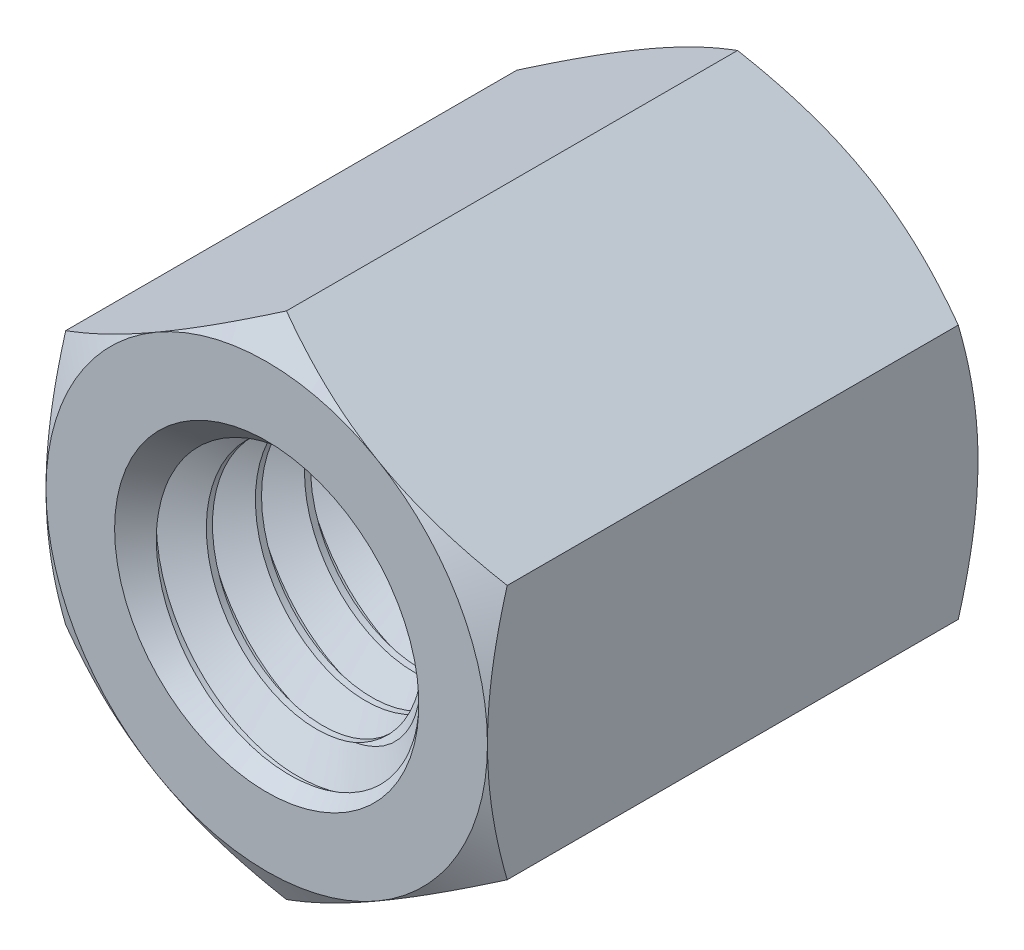
SolidWorks part; units mm, degrees
ref_plane "Front Plane" through (0, 0, 0) normal (0, 0, 1) x (1, 0, 0)
ref_plane "Top Plane" through (0, 0, 0) normal (0, 1, 0) x (1, 0, 0)
ref_plane "Right Plane" through (0, 0, 0) normal (1, 0, 0) x (0, 0, -1)
sketch "Sketch3" plane through (0, 0, 0) normal (1, 0, 0) x (0, 0, -1)
  line L0 (-2.5, 0) -> (2.5, 0) construction
  line L1 (0, 2.25) -> (0, -2.25) construction
  line L2 (-2.5, 1.5) -> (-2.5, -1.5) construction
  point P2 (-10.2, 0)
  point P3 (10.2, 0)
  dimension "D1" = 12.7
  dimension "Length" = 5
  dimension "Min Thread Length" = 12.7
  dimension "Thread Dia" = 3
  dimension "Hex" = 4.5
sketch "Sketch1" plane through (0, 0, 0) normal (0, 0, 1) x (1, 0, 0)
  line L1 (0, 2.5981) -> (-2.25, 1.299)
  line L2 (-2.25, 1.299) -> (-2.25, -1.299)
  line L3 (-2.25, -1.299) -> (0, -2.5981)
  line L4 (0, -2.5981) -> (2.25, -1.299)
  line L5 (2.25, -1.299) -> (2.25, 1.299)
  line L6 (2.25, 1.299) -> (0, 2.5981)
  circle A0 centre (0, 0) radius 2.25 construction
  circle A1 centre (0, 0) radius 1.5
extrude "Extrude1" add sketch "Sketch1" along normal up to vertex (2.5 mm away) and the other way up to vertex (2.5 mm away) up to point (0, 0, 2.5) other way up to point (0, 0, -2.5)
sketch "Sketch11" plane through (0, 0, -2.5) normal (0, 0, -1) x (-1, 0, 0)
  circle A0 centre (0, 0) radius 1.5 construction
  circle A1 centre (0, 0) radius 1.5
curve "Helix/Spiral1" pitch 0.5 height 5.5 radius 1.5 centre (0, 0, -2.5) axis (0, 0, 1) start towards (0, 1, 0) parameters "Pitch"=0.5
sketch "Sketch12" plane through (0, 0, 0) normal (1, 0, 0) x (0, 0, -1)
  line L0 (2.9375, 1.5) -> (2.5, 1.5)
  line L1 (2.9375, 1.5) -> (2.75, 1.1752)
  line L2 (2.75, 1.1752) -> (2.6875, 1.1752)
  line L3 (2.6875, 1.1752) -> (2.5, 1.5)
  line L4 (2.7188, 1.1752) -> (2.7188, 1.5) construction
  line L5 (2.8438, 1.3376) -> (2.5938, 1.3376) construction
  dimension "D1" = 0.0625
  dimension "D2" = 0.25
  dimension "D3" = 60
sweep "Sweep1" add profiles "Sketch12" path "Helix/Spiral1"
sketch "Sketch6" plane through (0, 0, -2.5) normal (0, 0, -1) x (-1, 0, 0)
  line L6 (0, 2.5981) -> (-2.25, 1.299)
  line L7 (-2.25, 1.299) -> (-2.25, -1.299)
  line L8 (-2.25, -1.299) -> (0, -2.5981)
  line L9 (0, -2.5981) -> (2.25, -1.299)
  line L10 (2.25, -1.299) -> (2.25, 1.299)
  line L11 (2.25, 1.299) -> (0, 2.5981)
  line L12 (0, 2.5981) -> (-2.25, 1.299)
  line L13 (-2.25, 1.299) -> (-2.25, -1.299)
  line L14 (-2.25, -1.299) -> (0, -2.5981)
  line L15 (0, -2.5981) -> (2.25, -1.299)
  line L16 (2.25, -1.299) -> (2.25, 1.299)
  line L17 (2.25, 1.299) -> (0, 2.5981)
  dimension "D1" = 0
extrude "Extrude2" cut sketch "Sketch6" along normal through all
sketch "Sketch7" plane through (0, 0, -2.5) normal (0, 0, -1) x (-1, 0, 0)
  circle A2 centre (0, 0) radius 1.5508
  circle A3 centre (0, 0) radius 1.5508
  dimension "D1" = 0.0508
extrude "Extrude3" cut sketch "Sketch7" against normal through all draft 43
sketch "Sketch8" plane through (0, 0, -2.5) normal (0, 0, -1) x (-1, 0, 0)
  circle A0 centre (0, 0) radius 2.25 construction
  circle A1 centre (0, 0) radius 2.25
extrude "Extrude4" cut sketch "Sketch8" against normal through all draft 60 flip side to cut
mirror "Mirror1" about plane through (0, 0, 0) normal (0, 0, 1) of "Extrude2", "Extrude3", "Extrude4"
sketch "Sketch9" [suppressed] plane through (0, 0, 0) normal (1, 0, 0) x (0, 0, -1)
  line L1 (-12.7, 2.4638) -> (12.7, 2.4638)
  line L2 (-12.7, 2.4638) -> (-12.7, 0)
  line L3 (-12.7, 0) -> (12.7, 0)
  line L4 (12.7, 2.4638) -> (12.7, 0)
  line L7 (-25.4, 0) -> (25.4, 0) construction
revolve "Revolve" [suppressed] add sketch "Sketch9" angle 360 about L0
sketch "Sketch10" [suppressed] plane through (0, 0, 0) normal (1, 0, 0) x (0, 0, -1)
  line L0 (25.4, 2.413) -> (12.7, 2.413)
  line L1 (-25.4, 2.413) -> (-12.7, 2.413)
  line L2 (12.7, 2.413) -> (12.7, -2.413)
  line L3 (-25.4, -2.4638) -> (-12.7, -2.4638)
  line L4 (-12.7, 2.413) -> (-12.7, -2.4638)
  line L5 (12.7, -2.413) -> (25.4, -2.413)
sketch "Sketch13" plane through (0, 0, 2.5) normal (0, 0, 1) x (1, 0, 0)
  line L0 (0.6959, 0.4402) -> (1.0897, 0.4402) construction
  line L1 (0.6959, 0.4402) -> (0.6959, -0.3853) construction
  line L2 (0.6959, 0.4402) -> (3.8103, 3.3481) construction
  arc A0 (0.5013, -1.063) -> (1.1082, -0.3912) centre (0, 0) ccw construction
  point P0 (0.6959, 0.4402)
  point P8 (-11.7542, 6.7404)
  point P9 (3.8103, 3.3481)
  point P10 (3.8103, 3.3481)
  point P11 (1.0897, 0.4402)
equation "\"D1@Sketch3\" = \"Min Thread Length@Sketch3\""
equation "\"D3@Helix/Spiral1\" = \"Length@Sketch3\"+\"Pitch@Helix/Spiral1\""
equation "\"D1@Sketch12\" = \"Pitch@Helix/Spiral1\"*.125"
equation "\"D2@Sketch12\" = \"Pitch@Helix/Spiral1\"*.5"
